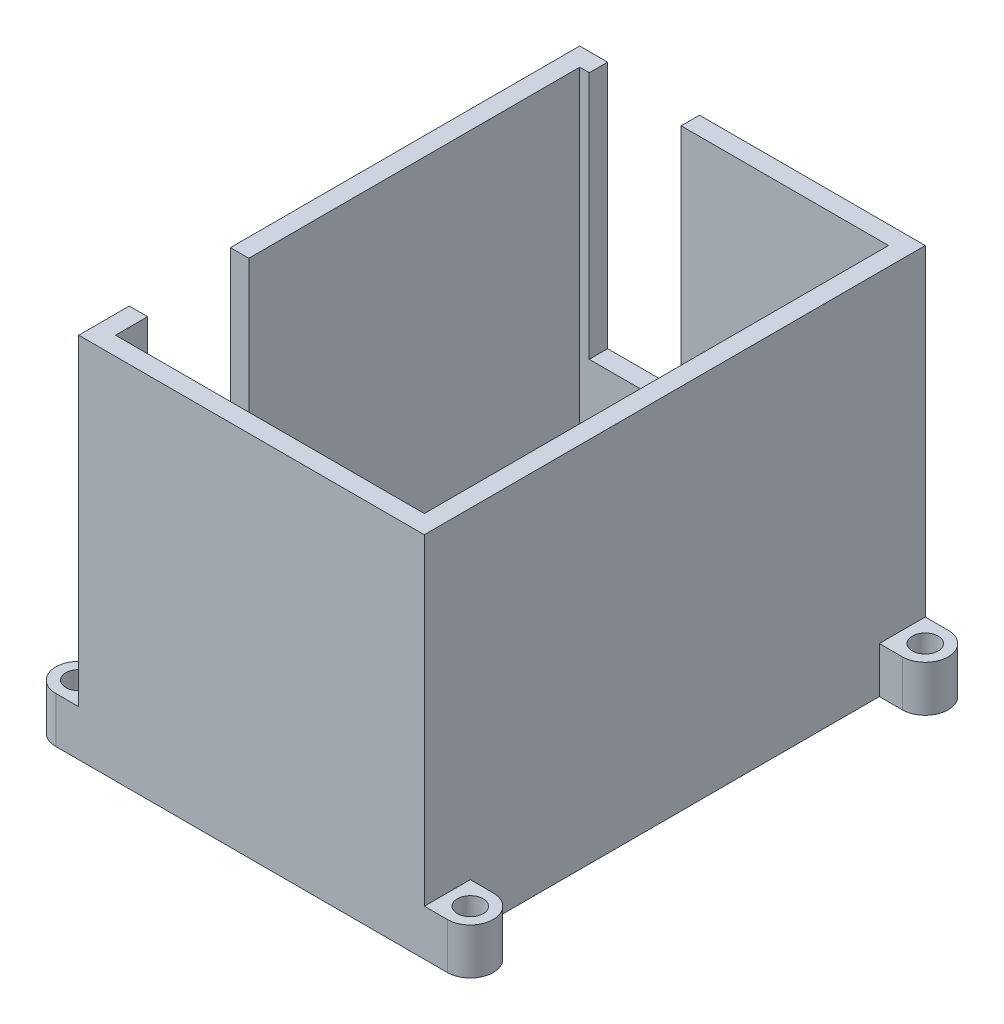
SolidWorks part; units mm, degrees
ref_plane "Front Plane" through (0, 0, 0) normal (0, 0, 1) x (1, 0, 0)
ref_plane "Top Plane" through (0, 0, 0) normal (0, 1, 0) x (1, 0, 0)
ref_plane "Right Plane" through (0, 0, 0) normal (1, 0, 0) x (0, 0, -1)
sketch "Sketch1" plane through (0, 0, 0) normal (0, 1, 0) x (1, 0, 0)
  line L1 (0, 0) -> (42.672, 0)
  line L2 (0, 0) -> (0, 64.135)
  line L3 (0, 64.135) -> (42.672, 64.135)
  line L4 (42.672, 0) -> (42.672, 64.135)
  line L5 (-2.54, 66.675) -> (45.212, 66.675)
  line L6 (-2.54, 66.675) -> (-2.54, -2.54)
  line L7 (-2.54, -2.54) -> (45.212, -2.54)
  line L8 (45.212, 66.675) -> (45.212, -2.54)
  dimension "D1" = 64.135
  dimension "D2" = 42.672
  dimension "D3" = 2.54
  dimension "D4" = 2.54
  dimension "D5" = 2.54
  dimension "D6" = 2.54
extrude "Boss-Extrude1" add sketch "Sketch1" along normal blind 50.8
sketch "Sketch2" plane through (0, 0, 0) normal (0, -1, 0) x (1, 0, 0)
  line L0 (-5.715, -3.81) -> (-2.54, -3.81)
  line L1 (-2.54, -3.81) -> (-2.54, 2.54)
  line L2 (-2.54, 2.54) -> (-5.715, 2.54)
  line L3 (-2.54, -66.675) -> (-2.54, 2.54) construction
  line L4 (-2.54, 2.54) -> (45.212, 2.54) construction
  line L7 (48.387, -60.325) -> (45.212, -60.325)
  line L9 (-2.54, -66.675) -> (-5.715, -66.675)
  line L10 (-2.54, -60.325) -> (-2.54, -66.675)
  line L11 (-5.715, -60.325) -> (-2.54, -60.325)
  line L12 (45.212, -60.325) -> (45.212, -66.675)
  line L13 (45.212, -66.675) -> (48.387, -66.675)
  line L14 (45.212, 2.54) -> (48.387, 2.54)
  line L15 (45.212, -3.81) -> (45.212, 2.54)
  line L16 (48.387, -3.81) -> (45.212, -3.81)
  arc A0 (-5.715, 2.54) -> (-5.715, -3.81) centre (-5.715, -0.635) ccw
  arc A1 (-5.715, -66.675) -> (-5.715, -60.325) centre (-5.715, -63.5) cw
  arc A2 (48.387, -66.675) -> (48.387, -60.325) centre (48.387, -63.5) ccw
  arc A3 (48.387, 2.54) -> (48.387, -3.81) centre (48.387, -0.635) cw
  dimension "D1" = 6.35
  dimension "D2" = 0
  dimension "D3" = 0
extrude "Boss-Extrude2" add sketch "Sketch2" against normal blind 6.35
hole_wizard "9/64 (0.14063) Diameter Hole1" positions "Sketch9" profile "Sketch10" hole size "9/64" standard "ANSI Inch" end condition through all
sketch "Sketch9" plane through (0, 6.35, 0) normal (0, 1, 0) x (1, 0, 0)
  point P0 (-5.715, 0.635)
  point P4 (-5.715, 63.5)
  point P7 (48.387, 63.5)
  point P10 (48.387, 0.635)
sketch "Sketch10" plane through (-5.715, 6.35, -0.635) normal (1, 0, 0) x (0, 0, 1)
  line L0 (0, 0) -> (0, 6.35)
  line L1 (0, 6.35) -> (1.786, 6.35)
  line L2 (1.786, 6.35) -> (1.786, 0)
  line L5 (1.786, 0) -> (0, 0)
  line L11 (0, -6.35) -> (0, 107.95) construction
  dimension "Thru Hole Dia." = 3.572
  dimension "Thru Hole Depth" = 6.35
sketch "Sketch11" plane through (-2.54, 0, 0) normal (-1, 0, 0) x (0, 0, 1)
  line L0 (-66.675, 50.8) -> (2.54, 50.8) construction
  line L1 (-18.415, 50.8) -> (-4.445, 50.8)
  line L2 (-18.415, 50.8) -> (-18.415, 12.065)
  line L3 (-18.415, 12.065) -> (-4.445, 12.065)
  line L4 (-4.445, 50.8) -> (-4.445, 12.065)
  line L5 (2.54, 50.8) -> (2.54, 6.35) construction
  line L6 (-60.325, 0) -> (-3.81, 0) construction
  dimension "D1" = 6.985
  dimension "D2" = 13.97
  dimension "D3" = 12.065
extrude "Cut-Extrude1" cut sketch "Sketch11" against normal blind 6.35
sketch "Sketch12" plane through (0, 0, -66.675) normal (0, 0, -1) x (-1, 0, 0)
  line L0 (-45.212, 50.8) -> (2.54, 50.8) construction
  line L1 (-1.3208, 50.8) -> (-14.0208, 50.8)
  line L2 (-1.3208, 50.8) -> (-1.3208, 16.51)
  line L3 (-1.3208, 16.51) -> (-14.0208, 16.51)
  line L4 (-14.0208, 50.8) -> (-14.0208, 16.51)
  line L5 (2.54, 50.8) -> (2.54, 6.35) construction
  line L6 (-48.387, 0) -> (5.715, 0) construction
  dimension "D1" = 12.7
  dimension "D2" = 16.5608
  dimension "D3" = 16.51
extrude "Cut-Extrude2" cut sketch "Sketch12" against normal blind 6.35
